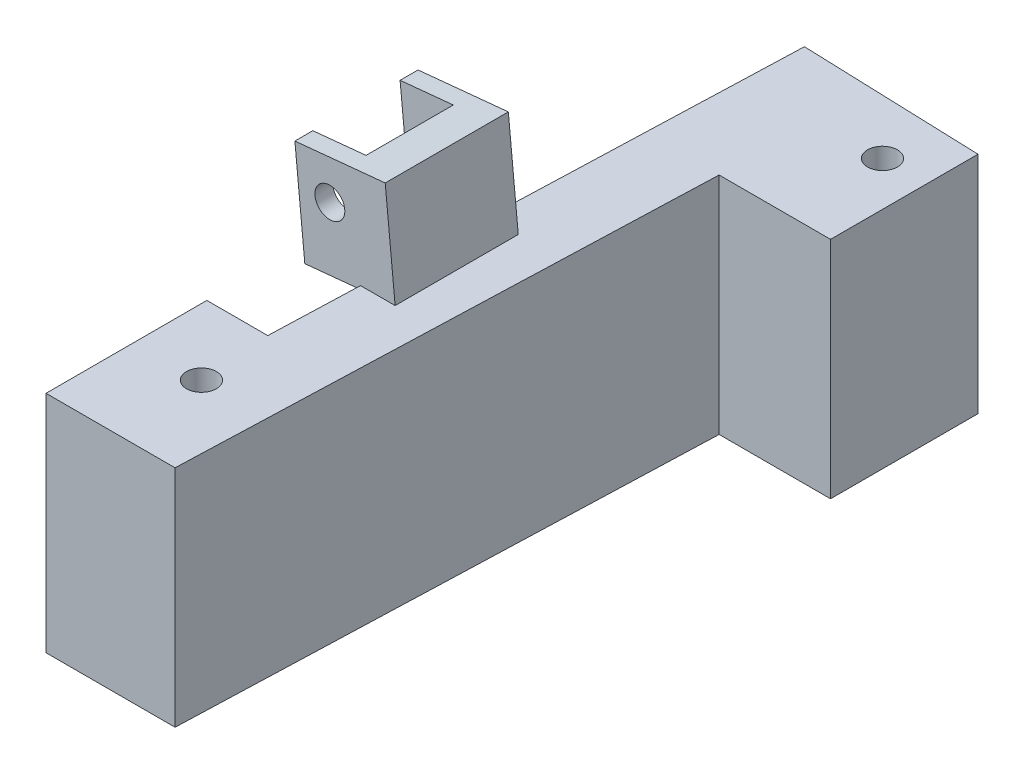
SolidWorks part; units mm, degrees
ref_plane "Front Plane" through (0, 0, 0) normal (0, 0, 1) x (1, 0, 0)
ref_plane "Top Plane" through (0, 0, 0) normal (0, 1, 0) x (1, 0, 0)
ref_plane "Right Plane" through (0, 0, 0) normal (1, 0, 0) x (0, 0, -1)
sketch "Sketch1" plane through (0, 0, 0) normal (0, 0, 1) x (1, 0, 0)
  line L0 (476.9237, 158.5913) -> (479.0335, 137.0791)
  line L1 (479.0335, 137.0791) -> (498.2247, 138.9613)
  line L2 (498.2247, 138.9613) -> (496.115, 160.4735)
  line L3 (496.115, 160.4735) -> (476.9237, 158.5913)
  line L4 (485.2846, 141.5205) -> (469.8952, 140.0112) construction
  line L5 (485.2846, 141.5205) -> (469.8952, 140.0112)
  arc A0 (489.9044, 158.7414) -> (483.4252, 160.4795) centre (484.3549, 151) ccw construction
  arc A1 (491.3026, 144.4842) -> (489.9044, 158.7414) centre (484.3549, 151) ccw construction
  arc A2 (485.2846, 141.5205) -> (491.3026, 144.4842) centre (484.3549, 151) ccw construction
  arc A3 (489.9044, 158.7414) -> (483.4252, 160.4795) centre (484.3549, 151) ccw
  arc A4 (491.3026, 144.4842) -> (489.9044, 158.7414) centre (484.3549, 151) ccw
  arc A5 (485.2846, 141.5205) -> (491.3026, 144.4842) centre (484.3549, 151) ccw
  dimension "D1" = 6.35
  dimension "D2" = 3.81
extrude "Boss-Extrude5" add sketch "Sketch1" against normal blind 22.352 contours A5 L5 L0 L1 L2 L3 A3 A4 region at (482.0029, 140.8922, 0)
sketch "Sketch2" plane through (0, 0, -22.352) normal (0, 0, -1) x (-1, 0, 0)
  line L0 (-488.2317, 159.7003) -> (-476.9237, 158.5913)
  line L1 (-476.9237, 158.5913) -> (-478.6616, 140.8709)
  line L2 (-478.6616, 140.8709) -> (-485.2846, 141.5205)
  arc A0 (-485.2846, 141.5205) -> (-488.2317, 159.7003) centre (-484.3549, 151) cw
  circle A1 centre (-484.3549, 151) radius 3.175 construction
  circle A2 centre (-484.3549, 151) radius 3.175
  circle A3 centre (-484.3549, 151) radius 3.175
  arc M5 (-485.2846, 141.5205) -> (-488.2317, 159.7003) centre (-484.3549, 151) cw
  line M10 (-478.6616, 140.8709) -> (-485.2846, 141.5205)
extrude "Boss-Extrude7" add sketch "Sketch2" against normal blind 3.81 contours L1 L0 A2 M5 M10 region at (482.6025, 158.8937, -22.352)
sketch "Sketch3" plane through (0, 0, 0) normal (0, 0, 1) x (1, 0, 0)
  line L0 (476.9237, 158.5913) -> (479.0335, 137.0791)
  line L1 (479.0335, 137.0791) -> (498.2247, 138.9613)
  line L2 (498.2247, 138.9613) -> (496.115, 160.4735)
  line L3 (496.115, 160.4735) -> (476.9237, 158.5913)
  circle A0 centre (484.3549, 151) radius 3.175 construction
  circle A1 centre (484.3549, 151) radius 3.175
  circle A2 centre (484.3549, 151) radius 3.175
  arc M6 (488.2317, 159.7003) -> (485.2846, 141.5205) centre (484.3549, 151) cw
  line M7 (485.2846, 141.5205) -> (478.6616, 140.8709)
  line M8 (478.6616, 140.8709) -> (479.0335, 137.0791)
  line M9 (479.0335, 137.0791) -> (498.2247, 138.9613)
  line M10 (498.2247, 138.9613) -> (496.115, 160.4735)
  line M11 (496.115, 160.4735) -> (488.2317, 159.7003)
extrude "Boss-Extrude8" add sketch "Sketch3" along normal blind 3.81 contours L3 L0 A1 M6 M7 | M11 M6 M7 M8 M9 M10 region at (482.6025, 158.8937, 0) region at (482.0029, 140.8922, 0)
ref_plane "Plane1" through (0, 138.9613, 0) normal (0, 1, 0) x (1, 0, 0)
sketch "Sketch4" plane through (0, 138.9613, 0) normal (0, 1, 0) x (1, 0, 0)
  line L0 (494.0725, 87.3113) -> (532.2914, 85.9701)
  line L2 (494.0725, 87.3113) -> (490.2062, -22.86)
  line L4 (508.6117, 54.6403) -> (504.6925, -57.0385)
  line L5 (532.2914, 85.9701) -> (532.2914, 54.6403)
  line L6 (532.2914, 54.6403) -> (508.6117, 54.6403)
  line L7 (504.6925, -57.0385) -> (477.2694, -57.0385)
  line L8 (477.2694, -57.0385) -> (477.2694, -22.86)
  line L9 (477.2694, -22.86) -> (490.2062, -22.86)
  dimension "D1" = 90
  dimension "D2" = 111.7476
  dimension "D3" = 180
  dimension "D4" = 110.1713
extrude "Boss-Extrude9" add sketch "Sketch4" against normal up to surface (47.7499 mm away)
sketch "Sketch6" plane through (0, 138.9613, 0) normal (0, 1, 0) x (1, 0, 0)
  circle A0 centre (491.3661, -38.1051) radius 3.175
  circle A1 centre (522.9171, 75.0492) radius 3.175
  dimension "D1" = 6.35
  dimension "D2" = 6.35
extrude "Cut-Extrude1" cut sketch "Sketch6" against normal blind 6.35
sketch "Sketch8" plane through (0, 138.9613, 0) normal (0, 1, 0) x (1, 0, 0)
  circle A0 centre (491.3661, -38.1051) radius 3.175
  circle A1 centre (522.9171, 75.0492) radius 3.175
  dimension "D1" = 6.35
  dimension "D2" = 6.35
extrude "Cut-Extrude2" cut sketch "Sketch8" against normal through all
